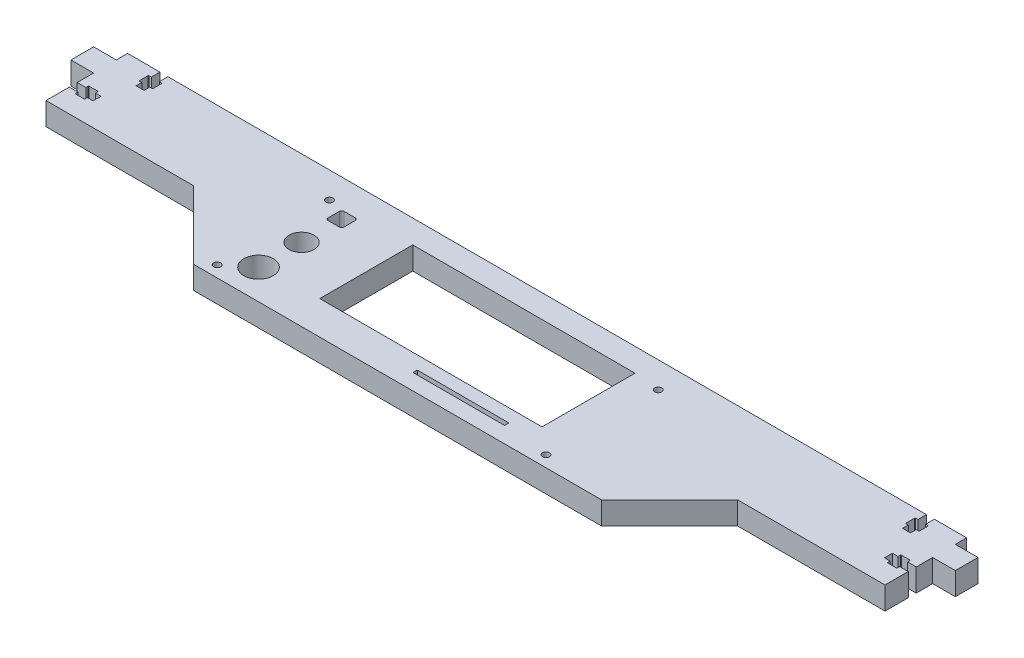
SolidWorks part; units mm, degrees
ref_plane "Front Plane" through (0, 0, 0) normal (0, 0, 1) x (1, 0, 0)
ref_plane "Top Plane" through (0, 0, 0) normal (0, 1, 0) x (1, 0, 0)
ref_plane "Right Plane" through (0, 0, 0) normal (1, 0, 0) x (0, 0, -1)
sketch "Sketch1" plane through (0, 0, 0) normal (0, 1, 0) x (1, 0, 0)
  line L0 (0, 18) -> (0, -18) construction
  line L1 (-185, 18) -> (0, 18)
  line L2 (-185, 18) -> (-185, 13)
  line L3 (-185, -18) -> (0, -18)
  line L4 (0, 18) -> (0, -18)
  line L5 (-185, 18) -> (0, 0) construction
  line L6 (-185, -18) -> (0, 0) construction
  line L7 (-185, 13) -> (-195, 13)
  line L8 (-195, 13) -> (-195, 3)
  line L9 (-195, 3) -> (-185, 3)
  line L10 (-185, 3) -> (-185, -18)
  point P0 (0, 0)
  dimension "D6" = 10
  dimension "D7" = 10
  dimension "D1" = 185
  dimension "D2" = 36
  dimension "D4" = 5
  dimension "D9" = 18
extrude "MainShape" add sketch "Sketch1" along normal blind 10 contours L2 L7 L8 L9 region at (-93.9423, 0, -0.1183)
sketch "Sketch2" plane through (0, 10, 0) normal (0, 1, 0) x (1, 0, 0)
  line L0 (-169, 18) -> (-169, 7.5) construction
  line L1 (-185, 18) -> (0, 18) construction
  line L2 (-170.75, 18) -> (-170.75, 14.2)
  line L3 (-170.75, 14.2) -> (-171.75, 14.2)
  line L4 (-172, 13.95) -> (-172, 10.25)
  line L5 (-171.75, 10) -> (-170.75, 10)
  line L6 (-170.75, 10) -> (-170.75, 7.5)
  line L7 (-170.75, 7.5) -> (-167.25, 7.5)
  line L8 (-185, 18) -> (-185, 13) construction
  line L9 (-170.75, 18) -> (-167.25, 18)
  line L10 (-167.25, 10) -> (-167.25, 7.5)
  line L11 (-166.25, 10) -> (-167.25, 10)
  line L12 (-166, 13.95) -> (-166, 10.25)
  line L13 (-167.25, 14.2) -> (-166.25, 14.2)
  line L14 (-167.25, 18) -> (-167.25, 14.2)
  line L16 (-185, -6) -> (-174.5, -6) construction
  line L50 (-185, 3) -> (-185, -18) construction
  line L51 (-174.5, -7.75) -> (-174.5, -4.25)
  line L52 (-174.5, -4.25) -> (-177, -4.25)
  line L53 (-177, -4.25) -> (-177, -3.25)
  line L54 (-177.25, -3) -> (-180.95, -3)
  line L55 (-181.2, -3.25) -> (-181.2, -4.25)
  line L56 (-181.2, -4.25) -> (-185, -4.25)
  line L57 (-185, -4.25) -> (-185, -7.75)
  line L58 (-195, 13) -> (-195, 3) construction
  line L59 (-181.2, -7.75) -> (-185, -7.75)
  line L60 (-181.2, -8.75) -> (-181.2, -7.75)
  line L61 (-177.25, -9) -> (-180.95, -9)
  line L62 (-177, -7.75) -> (-177, -8.75)
  line L63 (-174.5, -7.75) -> (-177, -7.75)
  arc A0 (-172, 10.25) -> (-171.75, 10) centre (-171.75, 10.25) ccw
  arc A1 (-171.75, 14.2) -> (-172, 13.95) centre (-171.75, 13.95) ccw
  arc A2 (-166.25, 14.2) -> (-166, 13.95) centre (-166.25, 13.95) cw
  arc A3 (-166, 10.25) -> (-166.25, 10) centre (-166.25, 10.25) cw
  arc A16 (-177, -3.25) -> (-177.25, -3) centre (-177.25, -3.25) ccw
  arc A17 (-180.95, -3) -> (-181.2, -3.25) centre (-180.95, -3.25) ccw
  arc A18 (-180.95, -9) -> (-181.2, -8.75) centre (-180.95, -8.75) cw
  arc A19 (-177, -8.75) -> (-177.25, -9) centre (-177.25, -8.75) cw
  point P14 (-172, 10)
  point P17 (-172, 14.2)
  point P28 (-166, 14.2)
  point P29 (-166, 10)
  point P34 (-195, 8)
  point P45 (-177, -3)
  point P48 (-181.2, -3)
  dimension "D8" = 0.25
  dimension "D16" = 0.25
  dimension "D1" = 10.5
  dimension "D2" = 1.75
  dimension "D3" = 1.75
  dimension "D4" = 8
  dimension "D5" = 3
  dimension "D6" = 4.2
  dimension "D7" = 16
  dimension "D9" = 10.5
  dimension "D10" = 8
  dimension "D11" = 4.2
  dimension "D12" = 3
  dimension "D13" = 1.75
  dimension "D14" = 1.75
  dimension "D15" = 14
extrude "ScrewSlots" cut sketch "Sketch2" against normal through all
mirror "Mirror1" about plane through (0, 0, 0) normal (1, 0, 0) of "ScrewSlots", "MainShape"
sketch "Sketch6" plane through (0, 10, 0) normal (0, 1, 0) x (1, 0, 0)
  line L0 (0, -18) -> (0, -48) construction
  line L2 (-185, -18) -> (185, -18) construction
  line L3 (90, -48) -> (-90, -48)
  line L4 (-90, -48) -> (-120, -18)
  line L5 (90, -48) -> (120, -18)
  line L6 (-120, -18) -> (120, -18)
  dimension "D1" = 135
  dimension "D2" = 30
  dimension "D3" = 90
extrude "Boss-Extrude1" add sketch "Sketch6" against normal through all
sketch "Sketch8" plane through (0, 10, 0) normal (0, 1, 0) x (1, 0, 0)
  line L0 (-71.5, 4.8833) -> (-77.5, 4.8833) construction
  line L1 (-77, -1.6167) -> (-72, -1.6167)
  line L2 (-78, -0.6167) -> (-78, 4.3833)
  line L3 (-77, 5.3833) -> (-72, 5.3833)
  line L4 (-71, -0.6167) -> (-71, 4.3833)
  line L5 (-78, -1.6167) -> (-71, 5.3833) construction
  line L6 (-78, 5.3833) -> (-71, -1.6167) construction
  line L7 (-71.5, -1.1167) -> (-71.5, 4.8833) construction
  circle A0 centre (-74.5, -34.7667) radius 6.5
  circle A1 centre (-74.5, -15.8167) radius 5.5
  arc A2 (-77, -1.6167) -> (-78, -0.6167) centre (-77, -0.6167) cw
  circle A3 centre (-74.5, -34.7667) radius 6 construction
  circle A4 centre (-74.5, -15.8167) radius 3.5 construction
  arc A5 (-72, -1.6167) -> (-71, -0.6167) centre (-72, -0.6167) ccw
  arc A6 (-72, 5.3833) -> (-71, 4.3833) centre (-72, 4.3833) cw
  arc A7 (-78, 4.3833) -> (-77, 5.3833) centre (-77, 4.3833) cw
  point P6 (-74.5, 1.8833)
  dimension "D1" = 0.5
  dimension "D2" = 2
  dimension "D3" = 0.5
  dimension "D5" = 1
  dimension "D4" = 0.5
extrude "Cut-Extrude2" cut sketch "Sketch8" against normal through all
sketch "Sketch7" plane through (0, 10, 0) normal (0, 1, 0) x (1, 0, 0)
  circle A0 centre (60.5, -43.0167) radius 1.55
  circle A1 centre (-84.5, -43.0167) radius 1.55
  circle A2 centre (-84.5, 6.4833) radius 1.55
  circle A3 centre (60.5, 6.4833) radius 1.55
  dimension "D1" = 3.1
  dimension "D2" = 3.1
  dimension "D3" = 3.1
  dimension "D4" = 3.1
extrude "Cut-Extrude1" cut sketch "Sketch7" against normal through all
sketch "Sketch9" plane through (0, 10, 0) normal (0, 1, 0) x (1, 0, 0)
  line L0 (0, 7.2333) -> (0, -32.7667) construction
  line L1 (48.5, 7.2333) -> (-48.5, 7.2333) construction
  line L2 (-48.5, -32.7667) -> (48.5, -32.7667) construction
  line L3 (-48.5, -12.7667) -> (48.5, -12.7667) construction
  line L4 (-48.5, 7.2333) -> (-48.5, -32.7667) construction
  line L5 (48.5, -32.7667) -> (48.5, 7.2333) construction
  line L7 (-49, -33.2667) -> (49, -33.2667)
  line L8 (-49, -33.2667) -> (-49, 7.7333)
  line L9 (-49, 7.7333) -> (49, 7.7333)
  line L10 (49, -33.2667) -> (49, 7.7333)
  line L11 (-49, -33.2667) -> (49, 7.7333) construction
  line L12 (-49, 7.7333) -> (49, -33.2667) construction
  point P12 (0, -12.7667)
  dimension "D1" = 0.5
  dimension "D2" = 0.5
extrude "Cut-Extrude3" cut sketch "Sketch9" against normal through all and the other way through all
sketch "Sketch10" plane through (0, 10, 0) normal (0, 1, 0) x (1, 0, 0)
  line L0 (20, -39.2667) -> (20, -40.7667) construction
  line L1 (40, -39.2667) -> (0, -39.2667) construction
  line L2 (0, -40.7667) -> (40, -40.7667) construction
  line L3 (0, -40.0167) -> (40, -40.0167) construction
  line L4 (0, -39.2667) -> (0, -40.7667) construction
  line L5 (40, -40.7667) -> (40, -39.2667) construction
  line L7 (-0.2, -40.9667) -> (40.2, -40.9667)
  line L8 (-0.2, -40.9667) -> (-0.2, -39.0667)
  line L9 (-0.2, -39.0667) -> (40.2, -39.0667)
  line L10 (40.2, -40.9667) -> (40.2, -39.0667)
  line L11 (-0.2, -40.9667) -> (40.2, -39.0667) construction
  line L12 (-0.2, -39.0667) -> (40.2, -40.9667) construction
  point P12 (20, -40.0167)
  dimension "D1" = 0.2
  dimension "D2" = 0.2
extrude "Cut-Extrude4" cut sketch "Sketch10" against normal through all
sketch "Sketch11" [suppressed] plane through (0, 0, 0) normal (0, -1, 0) x (1, 0, 0)
  line L1 (-149.5, -2.5) -> (-167.5, -2.5)
  line L2 (-147.5, -0.5) -> (-147.5, 6.5)
  line L3 (-149.5, 8.5) -> (-167.5, 8.5)
  line L4 (-169.5, -0.5) -> (-169.5, 6.5)
  line L5 (-147.5, -2.5) -> (-169.5, 8.5) construction
  line L6 (-147.5, 8.5) -> (-169.5, -2.5) construction
  line L7 (170.75, -7.5) -> (167.25, -7.5) construction
  line L8 (-174.5, 7.75) -> (-174.5, 4.25) construction
  arc A0 (-147.5, 6.5) -> (-149.5, 8.5) centre (-149.5, 6.5) ccw
  arc A1 (-167.5, 8.5) -> (-169.5, 6.5) centre (-167.5, 6.5) ccw
  arc A2 (-167.5, -2.5) -> (-169.5, -0.5) centre (-167.5, -0.5) cw
  arc A3 (-149.5, -2.5) -> (-147.5, -0.5) centre (-149.5, -0.5) ccw
  point P0 (-158.5, 3)
  dimension "D3" = 2
  dimension "D1" = 22
  dimension "D2" = 11
  dimension "D4" = 5
  dimension "D5" = 5
extrude "LCDCableCutout" [suppressed] cut sketch "Sketch11" against normal through all
equation "\"Y-ROD-SPACING\"=75"
equation "\"Y-BED-OFFSET\"=2"
equation "\"Y-BED-ROD-INSET\"=3.5"
equation "\"T-SLOT-NUT-FILLET-RADIUS\"=0.25"
equation "\"T-SLOT-SCREW-SHAFT-RADIUS\"=1.75"
equation "\"T-SLOT-SCREW-SHAFT-CUTOUT-LENGTH\"=10.5"
equation "\"T-SLOT-NUT-DEPTH\"=4.2"
equation "\"T-SLOT-NUT-WIDTH\"=3"
equation "\"T-SLOT-NUT-END-DISTANCE\"=8"
equation "\"ACRYLIC-TAB-CUTOUT-SIZE\"=\"ACRYLIC-THICKNESS\"+\"ACRYLIC-TAB-TOLERANCE\"*2"
equation "\"ACRYLIC-M3-HOLE\"=3.1"
equation "\"SMOOTHROD-CAP-SCREW-DISTANCE\"=20"
equation "\"D2@Sketch2\"=\"T-SLOT-SCREW-SHAFT-RADIUS\""
equation "\"D1@Sketch2\"=\"T-SLOT-SCREW-SHAFT-CUTOUT-LENGTH\""
equation "\"D6@Sketch2\"=\"T-SLOT-NUT-DEPTH\""
equation "\"D5@Sketch2\"=\"T-SLOT-NUT-WIDTH\""
equation "\"D3@Sketch2\"=\"T-SLOT-SCREW-SHAFT-RADIUS\""
equation "\"D8@Sketch2\"=\"T-SLOT-NUT-FILLET-RADIUS\""
equation "\"D4@Sketch2\"=\"T-SLOT-NUT-END-DISTANCE\""
equation "\"D11@Sketch2\"=\"T-SLOT-NUT-DEPTH\""
equation "\"D10@Sketch2\"=\"T-SLOT-NUT-END-DISTANCE\""
equation "\"D13@Sketch2\"=\"T-SLOT-SCREW-SHAFT-RADIUS\""
equation "\"D14@Sketch2\"=\"T-SLOT-SCREW-SHAFT-RADIUS\""
equation "\"D16@Sketch2\"=\"T-SLOT-NUT-FILLET-RADIUS\""
equation "\"D9@Sketch2\"=\"T-SLOT-SCREW-SHAFT-CUTOUT-LENGTH\""
equation "\"ACRYLIC-TAB-WIDTH\"=\"ACRYLIC-THICKNESS\""
equation "\"D6@Sketch1\"=\"ACRYLIC-TAB-WIDTH\""
equation "\"D7@Sketch1\"=\"ACRYLIC-TAB-WIDTH\""
equation "\"FRAME-WIDTH-INNER\"=370"
equation "\"D1@Sketch1\"=\"FRAME-WIDTH-INNER\"/2"
equation "\"X-ROD-SPACING\"=45"
equation "\"Z-ROD-SPACING\"=17.5"
equation "\"ACRYLIC-THICKNESS\"=10"
equation "\"ACRYLIC-THICKNESS2\"=4.5"
equation "\"NEMA17-HOLE-SPACING\"=31"
equation "\"NEMA17-CENTRAL-CUTOUT\"=22.5"
equation "\"Z-BRACKET-REACH\"=55"
equation "\"TOP-BRACKET-SPACING\"=40"
equation "\"SMOOTHROD-X-LENGTH\"=350"
equation "\"SMOOTHROD-Y-LENGTH\"=350"
equation "\"SMOOTHROD-Z-LENGTH\"=350"
equation "\"SMOOTHROD-TIGHTENING-HEADROOM\"=.25"
equation "\"LEADSCREW-Z-LENGTH\"=300"
equation "\"SCREW-LENGTH-FRAME\"=\"ACRYLIC-THICKNESS\" + 10"
equation "\"SCREW-HEAD-RADIUS\"=6"
equation "\"PRINTED-X-SMOOTHROD-DIAMETER\"=8.2"
equation "\"PRINTED-X-SMOOTHROD-CUTOUT\"=10"
equation "\"PRINTED-X-BASE-HEIGHT\"=10"
equation "\"PRINTED-LM8UU-CUTOUT-SIZE\"=15.25"
equation "\"PRINTED-LM8UU-CUTOUT-LENGTH\"=24.5"
equation "\"PRINTED-X-IDLER-HEIGHT\"=16"
equation "\"PSU-MOUNTING-WIDTH\"=95"
equation "\"PSU-MOUNTING-HEIGHT\"=177"
equation "\"D1@MainShape\"=\"ACRYLIC-THICKNESS\""
equation "\"Y-BELT-TO-ROD-DISTANCE\"=20"
equation "\"SPOOL-HOLDER-ROD-SPACING\"=150"
equation "\"Z-ROD-INSET\"=16"
equation "\"D7@Sketch2\"=\"Z-ROD-INSET\""
equation "\"D1@Sketch7\"=\"ACRYLIC-M3-HOLE\""
equation "\"D2@Sketch7\"=\"ACRYLIC-M3-HOLE\""
equation "\"D3@Sketch7\"=\"ACRYLIC-M3-HOLE\""
equation "\"D4@Sketch7\"=\"ACRYLIC-M3-HOLE\""
equation "\"Y-BED-SCREW-SPACING\"=209"
equation "\"Y-BED-SCREW-CUTOUT-SLOT-HEIGHT\"=2"
equation "\"ACRYLIC-TAB-TOLERANCE\"=.1"
equation "\"SCREW-LENGTH-MOTOR\"=\"ACRYLIC-THICKNESS\" + 5"
equation "\"SCREW-LENGTH-EXTRUDER\"=28"
equation "\"PRINTED-M3-HOLE\"=3.5"
equation "\"PRINTED-M3-NUT-AF\"=6.25"
equation "\"ACRYLIC-X-CARRIAGE-WIDTH\"=55"
equation "\"ACRYLIC-X-CARRIAGE-HEIGHT\"=75"
equation "\"ACRYLIC-X-CARRIAGE-LM8UU-CUTOUT-WIDTH\"=24.25"
equation "\"ACRYLIC-X-CARRIAGE-LM8UU-CUTOUT-HEIGHT\"=11.5"
equation "\"ACRYLIC-X-CARRIAGE-SCREW-SPACING-X\"=15"
equation "\"ACRYLIC-X-CARRIAGE-SCREW-SPACING-Y\"=33"
equation "\"ACRYLIC-X-CARRIAGE-CENTER-TAB-SPACING\"=14"
equation "\"ACRYLIC-X-CARRIAGE-EXTRUDER-OFFSET\"=26"
equation "\"ACRYLIC-X-CARRIAGE-EXTRUDER-ANGLE\"=90"
equation "\"ACRYLIC-X-CARRIAGE-EXTRUDER-SHELF-DEPTH\"=\"ACRYLIC-X-CARRIAGE-EXTRUDER-OFFSET\" + 28"
equation "\"ACRYLIC-X-CARRIAGE-EXTRUDER-BRACE-SPACING\"=23"
equation "\"ACRYLIC-X-CARRIAGE-EXTRUDER-BRACE-TAB-OFFSET\"=20"
equation "\"ACRYLIC-X-CARRIAGE-EXTRUDER-BRACE-HEIGHT\"=35"
equation "\"ACRYLIC-X-CARRIAGE-EXTRUDER-BRACE-SCREW-SPACING\"=22"
equation "\"ACRYLIC-X-CARRIAGE-DUAL-WIDTH-MULTIPLIER\"=1.65"
equation "\"ACRYLIC-X-CARRIAGE-DUAL-HOTEND-SPACING\"=42"
equation "\"ACRYLIC-X-CARRIAGE-DUAL-WIDTH\"=75"
equation "\"ACRYLIC-X-CARRIAGE-DUAL-HOTEND-SEPARATION\"=36"
equation "\"ACRYLIC-X-CARRIAGE-DUAL-MOUNT-PLATE-DEPTH\"=75"
equation "\"ACRYLIC-X-CARRIAGE-DUAL-MOUNT-BRACE-WIDTH\"=33"
equation "\"ACRYLIC-X-CARRIAGE-DUAL-MOUNT-SCREW-WIDTH\"=40"
equation "\"BLOWER-FAN-WIDTH\"=15"
